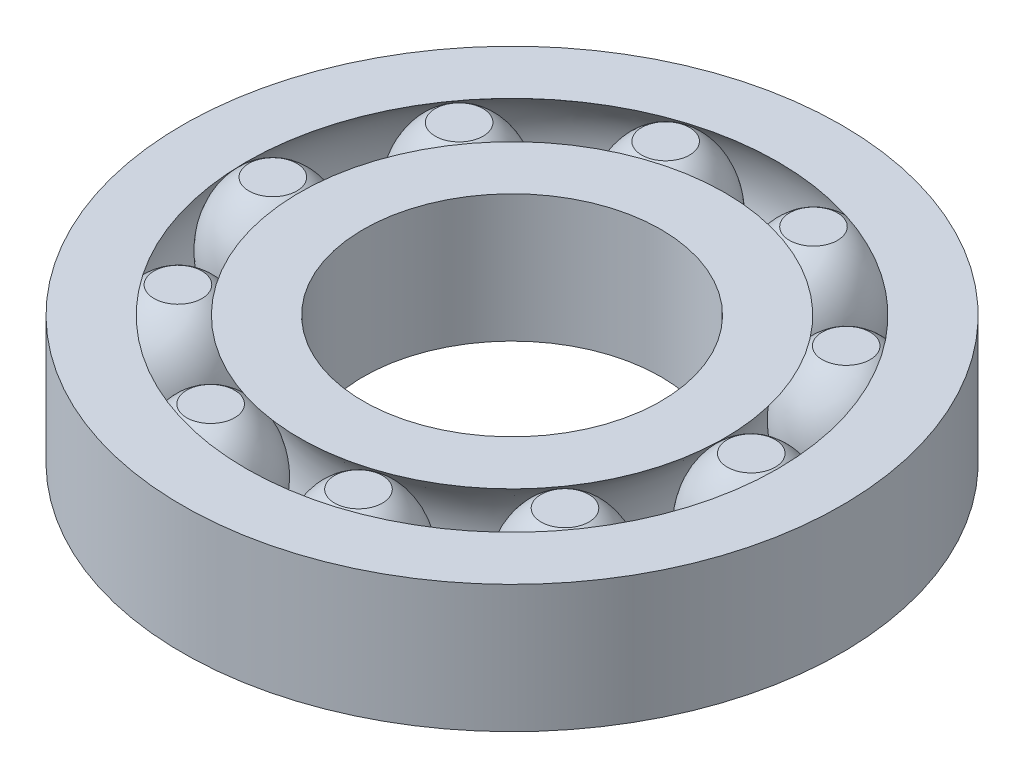
SolidWorks part; units mm, degrees
ref_plane "Front Plane" through (0, 0, 0) normal (0, 0, 1) x (1, 0, 0)
ref_plane "Top Plane" through (0, 0, 0) normal (0, 1, 0) x (1, 0, 0)
ref_plane "Right Plane" through (0, 0, 0) normal (1, 0, 0) x (0, 0, -1)
sketch "Sketch1" plane through (0, 0, 0) normal (0, 0, 1) x (1, 0, 0)
  line L1 (-7, 3) -> (-10, 3)
  line L4 (-11.25, 0) -> (-7, 0) construction
  line L7 (-11.25, 0) -> (-11.25, 3) construction
  line L13 (0, 0) -> (0, 4.657) construction
  line L14 (-7, 3) -> (-7, -3)
  line L15 (-11.25, 3) -> (-10.25, 3) construction
  line L16 (-7, -3) -> (-10, -3)
  line L17 (-15.5, -3) -> (-12.5, -3)
  line L18 (-15.5, 3) -> (-15.5, -3)
  line L19 (-15.5, 3) -> (-12.5, 3)
  ellipse E0 centre (-11.25, 0) end of major axis (-11.25, 3.2733) minor radius 2.5 (-8.75, 0) -> (-10.25, 3) ccw construction
  ellipse E1 centre (-11.25, 0) end of major axis (-11.25, 3.368) minor radius 2.75 (-10, 3) -> (-10, -3) cw
  ellipse E2 centre (-11.25, 0) end of major axis (-11.25, 3.368) minor radius 2.75 (-12.5, 3) -> (-12.5, -3) ccw
  point P2 (-14.951, 3.0175)
  point P6 (-13.9242, 0)
  point P12 (0, 0)
  point P14 (-16.3018, 0)
  point P31 (-8.5, 0)
  dimension "D4" = 1
  dimension "D1" = 7
  dimension "D2" = 3
  dimension "D3" = 3
  dimension "D5" = 0.25
  dimension "D6" = 2.5
  dimension "D7" = 0.25
  dimension "D8" = 3.2733
revolve "Revolve1" add sketch "Sketch1" angle 360 about L13
sketch "Sketch3" plane through (0, 0, 0) normal (0, 0, 1) x (1, 0, 0)
  line L0 (-11.25, 3) -> (-11.25, -3)
  line L2 (15.5, 3) -> (-15.5, 3) construction
  line L3 (-15.5, -3) -> (15.5, -3) construction
  line L6 (-10.125, -3) -> (-11.25, -3)
  line L7 (-7, 3) -> (-10, 3)
  line L8 (-7, -3) -> (-7, 3)
  line L9 (-10, -3) -> (-7, -3)
  line L10 (-7, 3) -> (-10, 3) construction
  line L11 (-7, -3) -> (-7, 3) construction
  line L12 (-10, -3) -> (-7, -3) construction
  line L13 (-12.5, 3) -> (-15.5, 3)
  line L14 (-15.5, -3) -> (-12.5, -3)
  line L15 (-15.5, 3) -> (-15.5, -3)
  line L16 (-12.5, 3) -> (-15.5, 3) construction
  line L17 (-15.5, -3) -> (-12.5, -3) construction
  line L18 (-15.5, 3) -> (-15.5, -3) construction
  line L19 (-11.25, 3) -> (-10.125, 3)
  ellipse E0 centre (-11.25, 0) end of major axis (-11.25, 3.3204) minor radius 2.625 (-10.125, -3) -> (-10.125, 3) ccw
  ellipse E1 centre (-11.25, 0) end of major axis (-11.25, 3.368) minor radius 2.75 (-10, -3) -> (-10, 3) ccw
  ellipse E2 centre (-11.25, 0) end of major axis (-11.25, 3.368) minor radius 2.75 (-10, -3) -> (-10, 3) ccw construction
  ellipse E3 centre (-11.25, 0) end of major axis (-11.25, 3.368) minor radius 2.75 (-12.5, 3) -> (-12.5, -3) ccw
  ellipse E4 centre (-11.25, 0) end of major axis (-11.25, 3.368) minor radius 2.75 (-12.5, 3) -> (-12.5, -3) ccw construction
  dimension "D1" = 0
  dimension "D2" = 0
  dimension "D3" = 0.125
  dimension "D4" = 0.125
  dimension "D5" = 0.125
revolve "Revolve2" add sketch "Sketch3" angle 360 about L0
ref_axis "Axis1" through (0, 3, 0) along (0, -1, 0)
pattern_circular "CirPattern7" count 10 over 360 about axis through (0, 3, 0) along (0, -1, 0) of bodies 105
